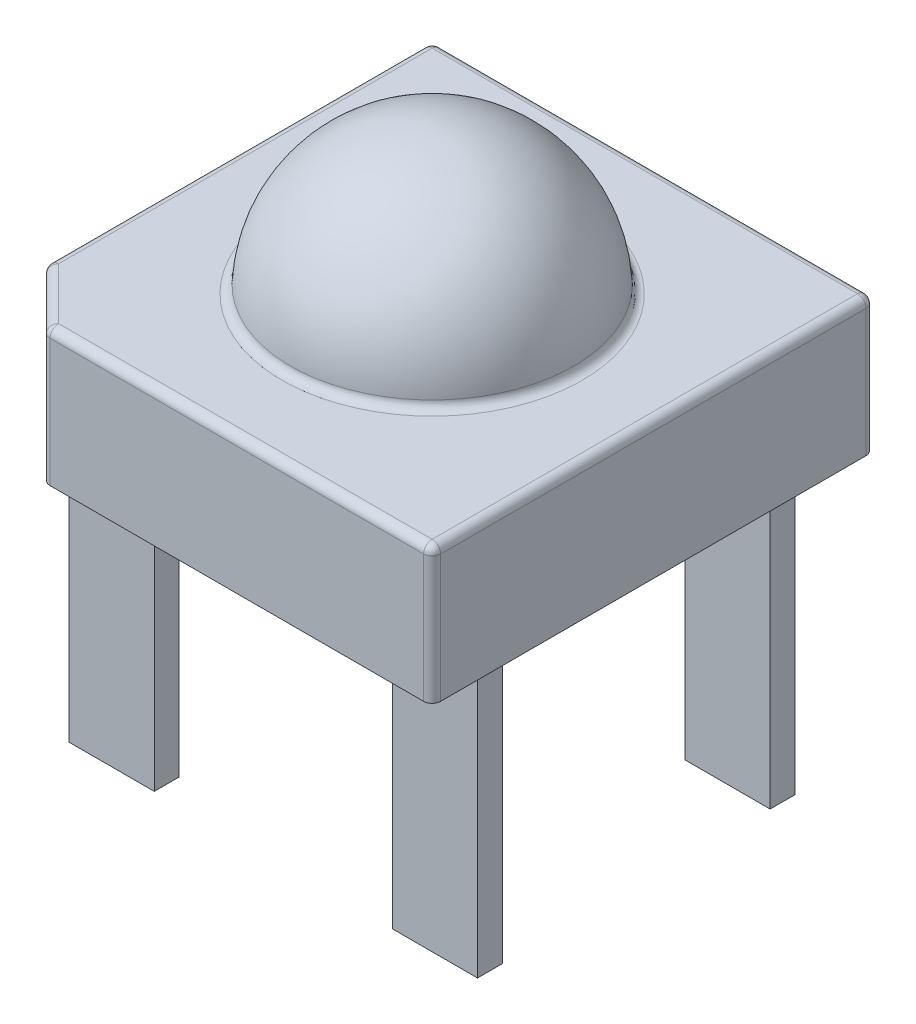
SolidWorks part; units mm, degrees
ref_plane "Front Plane" through (0, 0, 0) normal (0, 0, 1) x (1, 0, 0)
ref_plane "Top Plane" through (0, 0, 0) normal (0, 1, 0) x (1, 0, 0)
ref_plane "Right Plane" through (0, 0, 0) normal (1, 0, 0) x (0, 0, -1)
sketch "Sketch1" plane through (0, 0, 0) normal (0, 1, 0) x (1, 0, 0)
  line L0 (-3.9, 3.9) -> (3.9, -3.9) construction
  line L1 (-2.9, -3.9) -> (3.9, -3.9)
  line L2 (-3.9, -2.9) -> (-3.9, 3.9)
  line L3 (-3.9, 3.9) -> (3.9, 3.9)
  line L4 (3.9, -3.9) -> (3.9, 3.9)
  line L5 (-3.9, -2.9) -> (-2.9, -3.9)
  point P4 (0, 0)
  dimension "D1" = 1
  dimension "D2" = 7.8
  dimension "D3" = 1
  dimension "D4" = 7.8
extrude "Extrude1" add sketch "Sketch1" along normal blind 2.4
sketch "Sketch2" plane through (0, 0, 0) normal (0, 0, 1) x (1, 0, 0)
  line L0 (-2.9, 2.4) -> (3.9, 2.4) construction
  line L1 (-2.5, 2.4) -> (2.5, 2.4)
  line L2 (0, 2.4) -> (0, 4.9) construction
  arc A0 (2.5, 2.4) -> (-2.5, 2.4) centre (0, 2.4) ccw
  dimension "D1" = 5
revolve "Revolve1" add sketch "Sketch2" angle 360 about L2 region at (-1.061, 3.461, 0)
fillet "Fillet1" radius 0.15 11 edges at (0, 2.4, -2.5) (0.5, 2.4, 3.9) (-3.4, 2.4, 3.4) (-3.9, 2.4, -0.5) (0, 2.4, -3.9) (3.9, 2.4, 0) (-3.9, 1.2, -3.9) (3.9, 1.2, -3.9) (3.9, 1.2, 3.9) (-3.9, 1.2, 2.9) (-2.9, 1.2, 3.9)
sketch "Sketch3" plane through (0, 0, 0) normal (0, -1, 0) x (1, 0, 0)
  line L0 (0, 0) -> (0, 2.8) construction
  line L1 (-3.6, 2.8) -> (-2.1, 2.8)
  line L2 (-3.6, 2.8) -> (-3.6, 2.36)
  line L3 (-3.6, 2.36) -> (-2.1, 2.36)
  line L4 (-2.1, 2.8) -> (-2.1, 2.36)
  line L5 (0, 2.8) -> (-2.1, 2.8) construction
  line L6 (-3.9, -3.75) -> (-3.9, 2.8379) construction
  line L7 (2.1, 2.8) -> (2.1, 2.36)
  line L8 (3.6, 2.36) -> (2.1, 2.36)
  line L9 (3.6, 2.8) -> (3.6, 2.36)
  line L10 (3.6, 2.8) -> (2.1, 2.8)
  line L11 (0, 0) -> (-2.6864, 0) construction
  line L12 (3.6, -2.8) -> (3.6, -2.36)
  line L13 (3.6, -2.36) -> (2.1, -2.36)
  line L14 (3.6, -2.8) -> (2.1, -2.8)
  line L15 (2.1, -2.8) -> (2.1, -2.36)
  line L16 (-2.1, -2.8) -> (-2.1, -2.36)
  line L17 (-3.6, -2.8) -> (-2.1, -2.8)
  line L18 (-3.6, -2.8) -> (-3.6, -2.36)
  line L19 (-3.6, -2.36) -> (-2.1, -2.36)
  dimension "D1" = 0.44
  dimension "D2" = 1.5
  dimension "D3" = 0.3
  dimension "D4" = 2.8
extrude "Extrude2" add sketch "Sketch3" along normal blind 4.85
